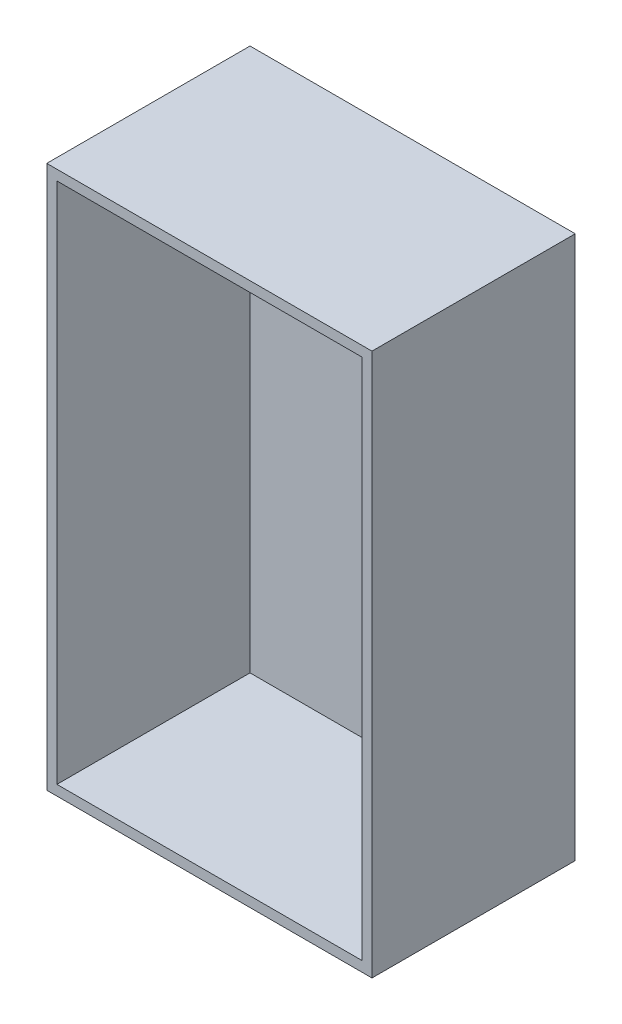
SolidWorks part; units mm, degrees
ref_plane "Front Plane" through (0, 0, 0) normal (0, 0, 1) x (1, 0, 0)
ref_plane "Top Plane" through (0, 0, 0) normal (0, 1, 0) x (1, 0, 0)
ref_plane "Right Plane" through (0, 0, 0) normal (1, 0, 0) x (0, 0, -1)
sketch "Sketch1" plane through (0, 0, 0) normal (0, 0, 1) x (1, 0, 0)
  line L0 (32, 98.419) -> (32, 100.419) construction
  line L1 (0, -6.419) -> (64, -6.419)
  line L2 (0, -6.419) -> (0, 100.419)
  line L3 (0, 100.419) -> (64, 100.419)
  line L4 (64, -6.419) -> (64, 100.419)
  line L5 (2, -4.419) -> (62, -4.419)
  line L6 (2, -4.419) -> (2, 98.419)
  line L7 (2, 98.419) -> (62, 98.419)
  line L8 (62, -4.419) -> (62, 98.419)
  line L9 (2, 47) -> (0, 47) construction
  line L10 (62, 47) -> (64, 47) construction
  line L11 (32, -4.419) -> (32, -6.419) construction
  line L12 (56.158, 97.419) -> (19.582, 97.419) construction
  line L13 (31.7232, -3.419) -> (44.0168, -3.419) construction
  point P19 (0, 0)
  dimension "D1" = 2
  dimension "D2" = 1
  dimension "D3" = 60
  dimension "D4" = 1
extrude "Boss-Extrude1" add sketch "Sketch1" along normal blind 2 contours L5 L8 L7 L6 | L1 L4 L3 L2 L8 L5 L6 L7 region at (1.2454, 47, 0) region at (32, 47, 0)
extrude "Boss-Extrude2" add sketch "Sketch1<3>" along normal blind 40
sketch "Sketch1<3>" plane through (0, 0, 0) normal (0, 0, 1) x (1, 0, 0) same geometry as "Sketch1"
